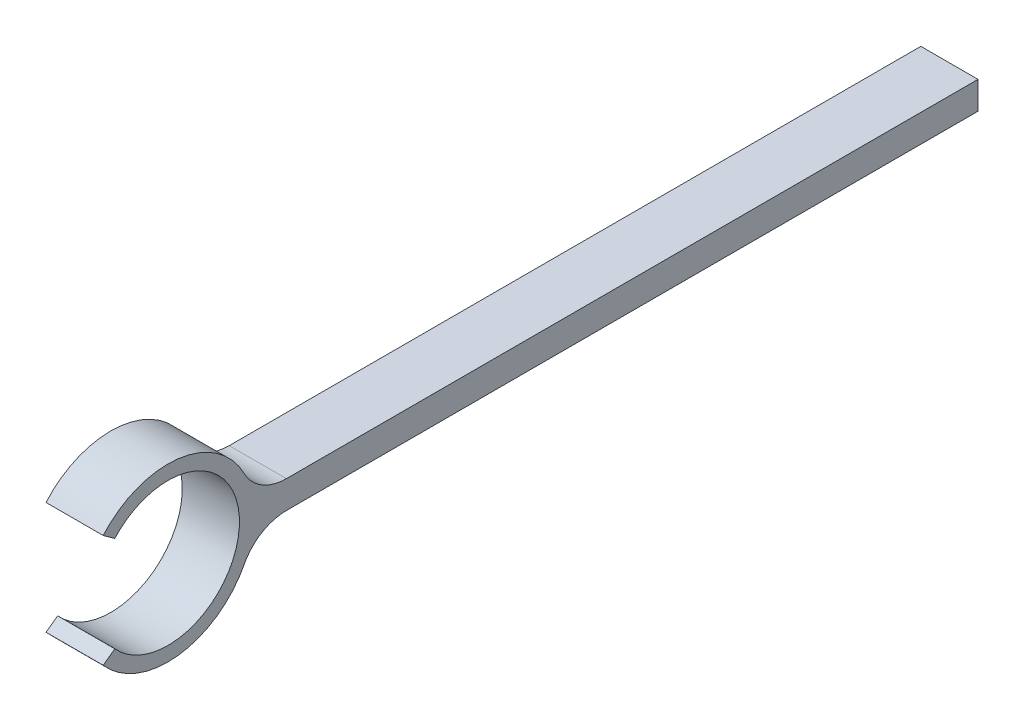
SolidWorks part; units mm, degrees
ref_plane "Front Plane" through (0, 0, 0) normal (0, 0, 1) x (1, 0, 0)
ref_plane "Top Plane" through (0, 0, 0) normal (0, 1, 0) x (1, 0, 0)
ref_plane "Right Plane" through (0, 0, 0) normal (1, 0, 0) x (0, 0, -1)
sketch "Sketch1" plane through (0, 0, 0) normal (1, 0, 0) x (0, 0, -1)
  line L0 (1.3952, 0) -> (-13.0645, 10.4065)
  line L1 (0, 0) -> (109.6696, 0) construction
  line L2 (8.8827, -1.4486) -> (85, -1.4486)
  line L3 (85, -1.4486) -> (85, 1.4486)
  line L4 (8.8827, 1.4486) -> (85, 1.4486)
  line L9 (15, 32.3322) -> (15, -32.3322) construction
  line L10 (1.3952, 0) -> (-13.0645, -10.4065)
  circle A0 centre (0, 0) radius 9
  circle A1 centre (0, 0) radius 7.5
  point P8 (25.0172, 0)
  point P10 (-10.9744, 12.2407)
  point P14 (85, 0)
  point P15 (-6.1545, 14.2454)
  point P18 (15, 0)
  point P19 (-11.1024, 13.2644)
  point P20 (-4.5763, 0)
  point P21 (-13.0645, 10.4065)
  point P22 (-2.6569, 0)
  point P23 (1.3952, 0)
  dimension "D1" = 15
  dimension "D2" = 1.5
  dimension "D4" = 70
extrude "Boss-Extrude1" add sketch "Sketch1" along normal blind 6 contours A1 A0 | A0 region at (0, 5.6513, 6.0471) region at (0, 0, -46.9805)
fillet "Fillet1" radius 5 2 edges at (3, 1.4486, -8.8827) (3, -1.4486, -8.8827)
